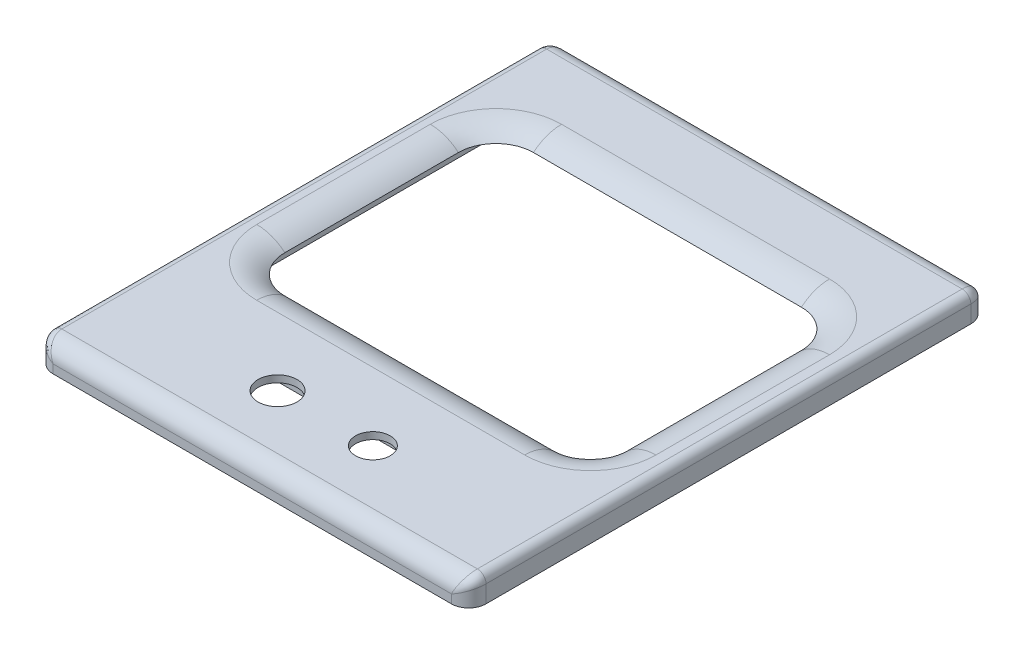
SolidWorks part; units mm, degrees
ref_plane "Front Plane" through (0, 0, 0) normal (0, 0, 1) x (1, 0, 0)
ref_plane "Top Plane" through (0, 0, 0) normal (0, 1, 0) x (1, 0, 0)
ref_plane "Right Plane" through (0, 0, 0) normal (1, 0, 0) x (0, 0, -1)
sketch "Sketch1" plane through (0, 0, 0) normal (0, 1, 0) x (1, 0, 0)
  line L1 (-25, 30) -> (25, 30)
  line L2 (-25, 30) -> (-25, -30)
  line L3 (-25, -30) -> (25, -30)
  line L4 (25, 30) -> (25, -30)
  line L5 (-25, 30) -> (25, -30) construction
  line L6 (-25, -30) -> (25, 30) construction
  point P0 (0, 0)
  dimension "D1" = 60
  dimension "D2" = 50
extrude "Boss-Extrude1" add sketch "Sketch1" along normal blind 3
sketch "Sketch2" plane through (0, 3, 0) normal (0, 1, 0) x (1, 0, 0)
  line L1 (-18.6141, 16.7575) -> (18.3356, 16.7575)
  line L2 (-18.6141, 16.7575) -> (-18.6141, -9.2891)
  line L3 (-18.6141, -9.2891) -> (18.3356, -9.2891)
  line L4 (18.3356, 16.7575) -> (18.3356, -9.2891)
  circle A0 centre (5.65, -21.72) radius 2
  circle A1 centre (-5.3614, -21.72) radius 2.25
  dimension "D1" = 4
  dimension "D2" = 4.5
extrude "Cut-Extrude1" cut sketch "Sketch2" against normal blind 10
fillet "Fillet1" radius 3 4 edges at (18.3356, 1.5, 9.2891) (-18.6141, 1.5, 9.2891) (18.3356, 1.5, -16.7575) (-18.6141, 1.5, -16.7575)
fillet "Fillet2" radius 5 8 edges at (-17.7354, 3, -15.8788) (-17.7354, 3, 8.4104) (-0.1392, 3, 9.2891) (17.457, 3, 8.4104) (17.457, 3, -15.8788) (-0.1392, 3, -16.7575) (18.3356, 3, -3.7342) (-18.6141, 3, -3.7342)
fillet "Fillet4" radius 1 2 edges at (-25, 3, 0) (25, 3, 0)
fillet "Fillet5" radius 2 10 edges at (-25, 1, 30) (-24.7071, 2.7071, 30) (25, 1, 30) (24.7071, 2.7071, 30) (25, 1, -30) (24.7071, 2.7071, -30) (-25, 1, -30) (-24.7071, 2.7071, -30) (0, 3, 30) (0, 3, -30)
sketch "Sketch3" plane through (0, 0, 0) normal (0, -1, 0) x (1, 0, 0)
  line L0 (0, 16.72) -> (0, 26.72) construction
  line L1 (10, 17.82) -> (-10, 17.82)
  line L2 (10, 17.82) -> (10, 25.62)
  line L3 (10, 25.62) -> (-10, 25.62)
  line L4 (-10, 17.82) -> (-10, 25.62)
  line L5 (10, 17.82) -> (-10, 25.62) construction
  line L6 (10, 25.62) -> (-10, 17.82) construction
  point P0 (0, 21.72)
extrude "Cut-Extrude2" cut sketch "Sketch3" against normal blind 2.2
sketch "Sketch4" plane through (0, 0, 0) normal (0, -1, 0) x (-1, 0, 0)
  line L0 (20.225, 23.4) -> (-19.815, -10.72) construction
  line L1 (-19.815, -10.72) -> (-19.815, 23.4) construction
  line L2 (-19.815, 23.4) -> (20.225, -10.72) construction
  line L3 (20.225, -10.72) -> (0.205, 6.34) construction
  line L5 (-20.795, 24.34) -> (21.205, 24.34)
  line L6 (-20.795, 24.34) -> (-20.795, -11.66)
  line L7 (-20.795, -11.66) -> (21.205, -11.66)
  line L8 (21.205, 24.34) -> (21.205, -11.66)
  line L9 (-20.795, 24.34) -> (21.205, -11.66) construction
  line L10 (-20.795, -11.66) -> (21.205, 24.34) construction
  dimension "D1" = 36
  dimension "D2" = 42
extrude "Cut-Extrude3" cut sketch "Sketch4" against normal blind 1.8
